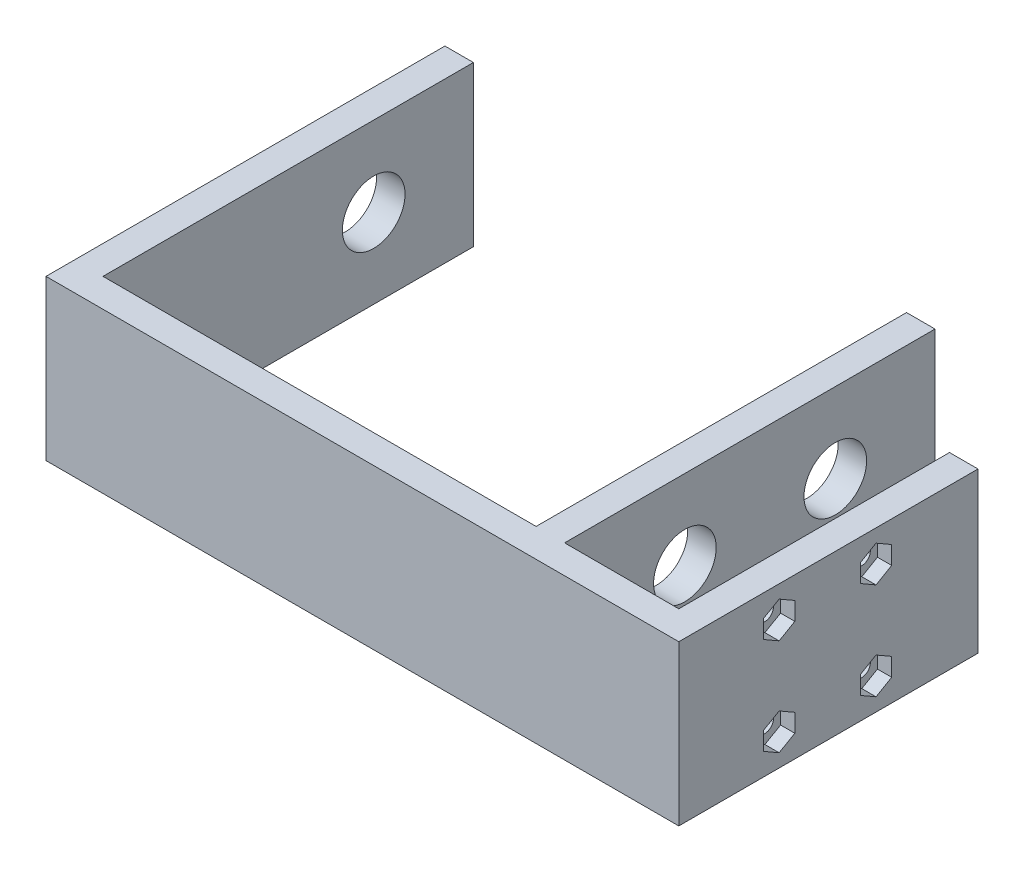
SolidWorks part; units mm, degrees
ref_plane "Front Plane" through (0, 0, 0) normal (0, 0, 1) x (1, 0, 0)
ref_plane "Top Plane" through (0, 0, 0) normal (0, 1, 0) x (1, 0, 0)
ref_plane "Right Plane" through (0, 0, 0) normal (1, 0, 0) x (0, 0, -1)
sketch "Sketch1" plane through (0, 0, 0) normal (0, 1, 0) x (1, 0, 0)
  line L0 (-35, -22.5) -> (-35, 22.5) construction
  line L1 (-30, -17.5) -> (30, -17.5) construction
  line L2 (-30, -17.5) -> (-30, 17.5) construction
  line L3 (-30, 17.5) -> (30, 17.5) construction
  line L4 (30, -17.5) -> (30, 17.5) construction
  line L5 (-30, -17.5) -> (30, 17.5) construction
  line L6 (-30, 17.5) -> (30, -17.5) construction
  line L7 (-35, 22.5) -> (35, 22.5) construction
  line L8 (35, -22.5) -> (35, 22.5) construction
  line L9 (-35, -22.5) -> (35, -22.5) construction
  line L10 (35, 0) -> (38, 0) construction
  line L11 (-35, 0) -> (-38, 0) construction
  line L12 (38, 0) -> (38, -22.5)
  line L13 (38, -22.5) -> (38, -47.5)
  line L14 (-38, 0) -> (-38, -22.5)
  line L15 (-38, -22.5) -> (-38, -47.5)
  line L16 (-38, -47.5) -> (38, -47.5)
  line L17 (38, 0) -> (38, 17.5)
  line L18 (-38, 0) -> (-38, 17.5)
  line L19 (-43, 0) -> (-43, 17.5)
  line L20 (-43, 0) -> (-43, -22.5)
  line L21 (-43, -22.5) -> (-43, -52.5)
  line L22 (-43, -52.5) -> (43, -52.5)
  line L23 (43, -22.5) -> (43, -52.5) construction
  line L24 (43, 0) -> (43, -22.5)
  line L25 (43, 0) -> (43, 17.5)
  line L26 (-38, 17.5) -> (-43, 17.5)
  line L27 (38, 17.5) -> (43, 17.5)
  line L28 (63.04, -47.5) -> (63.04, 0)
  line L29 (43, -52.5) -> (63.04, -52.5)
  line L31 (43, -47.5) -> (63.04, -47.5)
  line L32 (63.04, -52.5) -> (63.04, -47.5) construction
  line L33 (63.04, -52.5) -> (68.04, -52.5)
  line L34 (63.04, -52.5) -> (63.04, 0) construction
  line L35 (63.04, 0) -> (68.04, 0)
  line L36 (68.04, -52.5) -> (68.04, 0)
  line L37 (43, -47.5) -> (43, 17.5)
  point P0 (0, 0)
  point P10 (35, 0)
  point P11 (0, -22.5)
  point P12 (0, 22.5)
  point P13 (-35, 0)
  dimension "D1" = 60
  dimension "D2" = 35
  dimension "D4" = 3
  dimension "D5" = 25
  dimension "D7" = 20.04
  dimension "D8" = 5
  dimension "D3" = 5
  dimension "D6" = 5
extrude "Boss-Extrude1" add sketch "Sketch1" along normal mid plane 28 contours L31 L37 L24 L25 L27 L17 L12 L13 L16 L15 L14 L18 L26 L19 L20 L21 L22 L29 L33 L36 L35 L28 region at (39.3126, 0, -8.75)
sketch "Sketch2" plane through (43, 0, 0) normal (1, 0, 0) x (0, 0, -1)
  line L0 (-23.594, 0) -> (-26.9808, 0) construction
  line L1 (-23.594, 0) -> (-26.394, 0) construction
  line L4 (-47.5, -14) -> (17.5, -14)
  line L5 (17.5, -14) -> (17.5, 14)
  line L6 (-47.5, -14) -> (17.5, -14)
  line L7 (17.5, 14) -> (-47.5, 14)
  line L9 (17.5, -14) -> (17.5, 14)
  line L14 (17.5, 14) -> (-47.5, 14)
  line L15 (-47.5, 14) -> (-47.5, -14)
  line L16 (-47.5, 14) -> (-47.5, -14)
  circle A0 centre (0, 0) radius 5.5
  circle A1 centre (0, 0) radius 23.594 construction
  circle A2 centre (-26.394, 0) radius 3.3868 construction
  circle A3 centre (-26.9808, 0) radius 3.3867 construction
  circle A4 centre (-26.394, 0) radius 5.5
  dimension "D2" = 11
  dimension "D3" = 47.188
  dimension "D4" = 3.3868
  dimension "D5" = 2.8
  dimension "D1" = 0
extrude "Cut-Extrude1" cut sketch "Sketch2" against normal up to surface (86 mm away) contours A0 up to face at (-43, 0, 17.5)
sketch "Sketch3" plane through (43, 0, 0) normal (1, 0, 0) x (0, 0, -1)
  circle A0 centre (-26.394, 0) radius 5.5 construction
  circle A1 centre (-26.394, 0) radius 5.5
extrude "Cut-Extrude2" cut sketch "Sketch3" against normal up to next
sketch "Sketch4" plane through (63.04, 0, 0) normal (-1, 0, 0) x (0, 0, 1)
  line L1 (14.894, -11.5) -> (37.894, -11.5)
  line L2 (14.894, -11.5) -> (14.894, 11.5)
  line L3 (14.894, 11.5) -> (37.894, 11.5)
  line L4 (37.894, -11.5) -> (37.894, 11.5)
  line L5 (14.894, -11.5) -> (37.894, 11.5) construction
  line L6 (14.894, 11.5) -> (37.894, -11.5) construction
  line L7 (17.894, -8.5) -> (34.894, -8.5) construction
  line L8 (17.894, -8.5) -> (17.894, 8.5) construction
  line L9 (17.894, 8.5) -> (34.894, 8.5) construction
  line L10 (34.894, -8.5) -> (34.894, 8.5) construction
  line L11 (17.894, -8.5) -> (34.894, 8.5) construction
  line L12 (17.894, 8.5) -> (34.894, -8.5) construction
  circle A0 centre (17.894, 8.5) radius 1.85
  circle A1 centre (26.394, 0) radius 3
  circle A2 centre (26.394, 0) radius 3 construction
  circle A3 centre (34.894, 8.5) radius 1.85
  circle A4 centre (34.894, -8.5) radius 1.85
  circle A5 centre (17.894, -8.5) radius 1.85
  dimension "D6" = 3.7
  dimension "D2" = 23
  dimension "D3" = 23
  dimension "D4" = 17
  dimension "D5" = 17
  dimension "D1" = 0
sketch "Sketch6" plane through (68.04, 0, 0) normal (1, 0, 0) x (0, 0, -1)
  line L0 (-34.894, -5.2091) -> (-37.744, -6.8546) construction
  line L1 (-34.894, -5.3246) -> (-37.644, -6.9123)
  line L2 (-37.644, -6.9123) -> (-37.644, -10.0877)
  line L3 (-37.644, -10.0877) -> (-34.894, -11.6754)
  line L4 (-34.894, -11.6754) -> (-32.144, -10.0877)
  line L5 (-32.144, -10.0877) -> (-32.144, -6.9123)
  line L6 (-32.144, -6.9123) -> (-34.894, -5.3246)
  line L7 (-37.744, -6.8546) -> (-37.744, -10.1454) construction
  line L8 (-37.744, -10.1454) -> (-34.894, -11.7909) construction
  line L9 (-34.894, -11.7909) -> (-32.044, -10.1454) construction
  line L10 (-32.044, -10.1454) -> (-32.044, -6.8546) construction
  line L11 (-32.044, -6.8546) -> (-34.894, -5.2091) construction
  line L12 (-26.394, 1.435) -> (-26.394, -1.435) construction
  line L13 (-20.744, -6.8546) -> (-17.894, -5.2091) construction
  line L14 (-27.8, 0) -> (-24.988, 0) construction
  line L15 (-20.744, -10.1454) -> (-20.744, -6.8546) construction
  line L52 (-17.894, -11.7909) -> (-20.744, -10.1454) construction
  line L53 (-15.044, -10.1454) -> (-17.894, -11.7909) construction
  line L54 (-15.044, -6.8546) -> (-15.044, -10.1454) construction
  line L55 (-17.894, -5.2091) -> (-15.044, -6.8546) construction
  line L56 (-20.644, -6.9123) -> (-17.894, -5.3246)
  line L57 (-20.644, -10.0877) -> (-20.644, -6.9123)
  line L58 (-17.894, -11.6754) -> (-20.644, -10.0877)
  line L59 (-15.144, -10.0877) -> (-17.894, -11.6754)
  line L60 (-15.144, -6.9123) -> (-15.144, -10.0877)
  line L61 (-17.894, -5.3246) -> (-15.144, -6.9123)
  line L62 (-17.894, 5.2091) -> (-15.044, 6.8546) construction
  line L63 (-15.044, 6.8546) -> (-15.044, 10.1454) construction
  line L64 (-15.044, 10.1454) -> (-17.894, 11.7909) construction
  line L65 (-17.894, 11.7909) -> (-20.744, 10.1454) construction
  line L66 (-20.744, 10.1454) -> (-20.744, 6.8546) construction
  line L67 (-20.744, 6.8546) -> (-17.894, 5.2091) construction
  line L68 (-32.044, 6.8546) -> (-34.894, 5.2091) construction
  line L69 (-32.044, 10.1454) -> (-32.044, 6.8546) construction
  line L70 (-34.894, 11.7909) -> (-32.044, 10.1454) construction
  line L71 (-37.744, 10.1454) -> (-34.894, 11.7909) construction
  line L72 (-37.744, 6.8546) -> (-37.744, 10.1454) construction
  line L73 (-34.894, 5.2091) -> (-37.744, 6.8546) construction
  line L74 (-17.894, 5.3246) -> (-15.144, 6.9123)
  line L75 (-15.144, 6.9123) -> (-15.144, 10.0877)
  line L76 (-15.144, 10.0877) -> (-17.894, 11.6754)
  line L77 (-17.894, 11.6754) -> (-20.644, 10.0877)
  line L78 (-20.644, 10.0877) -> (-20.644, 6.9123)
  line L79 (-20.644, 6.9123) -> (-17.894, 5.3246)
  line L80 (-32.144, 6.9123) -> (-34.894, 5.3246)
  line L81 (-32.144, 10.0877) -> (-32.144, 6.9123)
  line L82 (-34.894, 11.6754) -> (-32.144, 10.0877)
  line L83 (-37.644, 10.0877) -> (-34.894, 11.6754)
  line L84 (-37.644, 6.9123) -> (-37.644, 10.0877)
  line L85 (-34.894, 5.3246) -> (-37.644, 6.9123)
  circle A3 centre (-34.894, -8.5) radius 1.85 construction
  circle A7 centre (-34.894, -8.5) radius 1.85 construction
  circle A8 centre (-34.894, -8.5) radius 2.75 construction
  circle A16 centre (-17.894, -8.5) radius 2.75 construction
  circle A17 centre (-17.894, -8.5) radius 1.85 construction
  circle A18 centre (-17.894, 8.5) radius 1.85 construction
  circle A19 centre (-17.894, 8.5) radius 2.75 construction
  circle A20 centre (-34.894, 8.5) radius 2.75 construction
  circle A21 centre (-34.894, 8.5) radius 1.85 construction
  point P29 (-26.394, 0)
  point P33 (-26.394, 0)
  dimension "D2" = 5.5
  dimension "D1" = 0.1
extrude "Cut-Extrude3" cut sketch "Sketch6" against normal blind 2.5
extrude "Boss-Extrude3" add sketch "Sketch4" along normal blind 1 contours A0 | A3 | A4 | A5 region at (63.04, 8.5, 17.894) region at (63.04, 8.5, 34.894) region at (63.04, -8.5, 34.894) region at (63.04, -8.5, 17.894)
sketch "Sketch7" plane through (62.04, 0, 0) normal (-1, 0, 0) x (0, 0, 1)
  circle A0 centre (34.894, 8.5) radius 1.5
  circle A1 centre (17.894, 8.5) radius 1.5
  circle A2 centre (34.894, -8.5) radius 1.85
  circle A3 centre (34.894, -8.5) radius 1.85
  circle A4 centre (17.894, 8.5) radius 1.85
  circle A5 centre (17.894, 8.5) radius 1.85
  circle A6 centre (17.894, -8.5) radius 1.85
  circle A7 centre (17.894, -8.5) radius 1.85
  circle A8 centre (17.894, -8.5) radius 1.5
  circle A9 centre (34.894, -8.5) radius 1.5
  dimension "D1" = 3
  dimension "D2" = 0
  dimension "D3" = 0
  dimension "D4" = 0
extrude "Cut-Extrude4" cut sketch "Sketch7" against normal up to next contours A8 | A9 | A0 | A1 region at (62.04, 8.5, 34.894) region at (62.04, -8.5, 17.894) region at (62.04, -8.5, 34.894)
equation "\"a\"= 1"
equation "\"b\"= 1"
equation "\"c\"= 1"
equation "\"d\"= 1"
equation "\"e\"= 1"
equation "\"x\"= 1"
equation "\"y\"= 1"
equation "\"z\"= 1"
